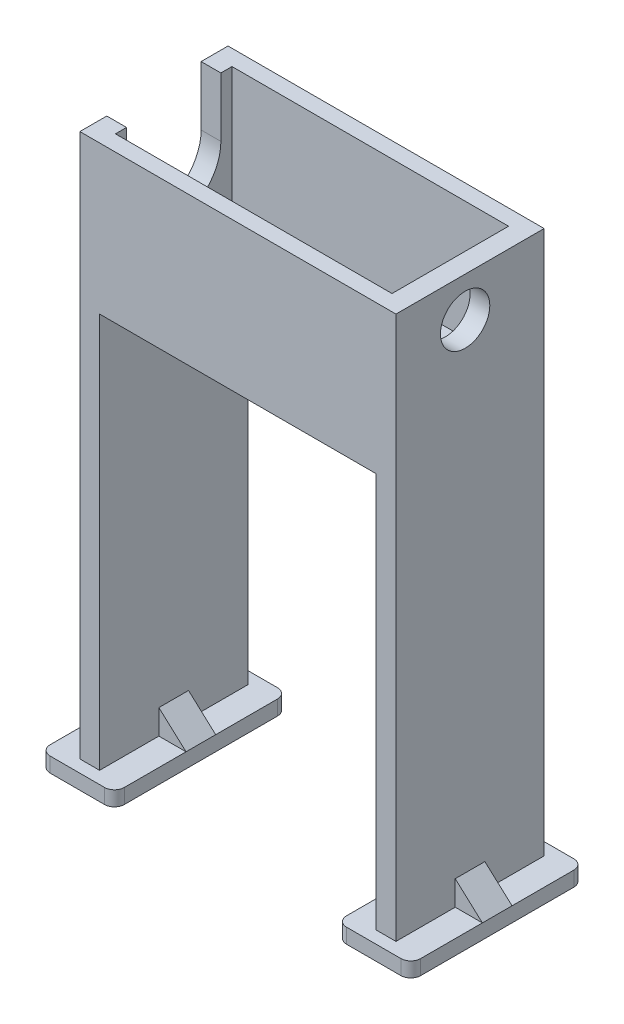
SolidWorks part; units mm, degrees
material "ABS"
ref_plane "Alzado" through (0, 0, 0) normal (0, 0, 1) x (1, 0, 0)
ref_plane "Planta" through (0, 0, 0) normal (0, 1, 0) x (1, 0, 0)
ref_plane "Vista lateral" through (0, 0, 0) normal (1, 0, 0) x (0, 0, -1)
sketch "Croquis2" plane through (0, 0, 0) normal (0, 1, 0) x (1, 0, 0)
  line L0 (30, 22.5259) -> (30, -22.5259) construction
  line L1 (-5.5, -17.5) -> (5.5, -17.5)
  line L2 (-7.5, -15.5) -> (-7.5, 15.5)
  line L3 (-5.5, 17.5) -> (5.5, 17.5)
  line L4 (7.5, -15.5) -> (7.5, 15.5)
  line L5 (-7.5, -17.5) -> (7.5, 17.5) construction
  line L6 (-7.5, 17.5) -> (7.5, -17.5) construction
  line L7 (67.5, 17.5) -> (52.5, -17.5) construction
  line L8 (67.5, -17.5) -> (52.5, 17.5) construction
  line L9 (52.5, -15.5) -> (52.5, 15.5)
  line L10 (65.5, 17.5) -> (54.5, 17.5)
  line L11 (67.5, -15.5) -> (67.5, 15.5)
  line L12 (65.5, -17.5) -> (54.5, -17.5)
  arc A0 (-5.5, -17.5) -> (-7.5, -15.5) centre (-5.5, -15.5) cw
  arc A1 (5.5, -17.5) -> (7.5, -15.5) centre (5.5, -15.5) ccw
  arc A2 (5.5, 17.5) -> (7.5, 15.5) centre (5.5, 15.5) cw
  arc A3 (-7.5, 15.5) -> (-5.5, 17.5) centre (-5.5, 15.5) cw
  arc A4 (67.5, 15.5) -> (65.5, 17.5) centre (65.5, 15.5) ccw
  arc A5 (54.5, 17.5) -> (52.5, 15.5) centre (54.5, 15.5) ccw
  arc A6 (54.5, -17.5) -> (52.5, -15.5) centre (54.5, -15.5) cw
  arc A7 (65.5, -17.5) -> (67.5, -15.5) centre (65.5, -15.5) ccw
  point P0 (0, 0)
  point P36 (60, 0)
  dimension "D4" = 2
  dimension "D1" = 60
  dimension "D2" = 15
  dimension "D3" = 35
extrude "Saliente-Extruir1" add sketch "Croquis2" along normal blind 3
sketch "Croquis3" plane through (0, 0, 0) normal (0, 0, 1) x (1, 0, 0)
  line L0 (-7.5, 3) -> (-2, 8)
  line L1 (-2, 8) -> (-2, 3)
  line L2 (-5.5, 3) -> (5.5, 3) construction
  line L3 (-2, 3) -> (-7.5, 3)
  line L4 (0, 0) -> (0, 24.6277) construction
  line L5 (0, 0) -> (60, 0) construction
  line L6 (54.5, 0) -> (65.5, 0) construction
  line L7 (30, 0) -> (30, 25.119) construction
  line L8 (2, 3) -> (7.5, 3)
  line L9 (2, 8) -> (2, 3)
  line L10 (7.5, 3) -> (2, 8)
  line L11 (52.5, 3) -> (58, 8)
  line L12 (58, 8) -> (58, 3)
  line L13 (58, 3) -> (52.5, 3)
  line L14 (62, 3) -> (67.5, 3)
  line L15 (62, 8) -> (62, 3)
  line L16 (67.5, 3) -> (62, 8)
  dimension "D1" = 5.5
  dimension "D2" = 5
extrude "Saliente-Extruir2" add sketch "Croquis3" along normal blind 3 and the other way blind 3
sketch "Croquis4" plane through (0, 3, 0) normal (0, 1, 0) x (1, 0, 0)
  line L0 (0, 0) -> (60, 0) construction
  line L1 (-2, -15) -> (2, -15)
  line L2 (-2, -15) -> (-2, 15)
  line L3 (-2, 15) -> (2, 15)
  line L4 (2, -15) -> (2, 15)
  line L5 (-2, -15) -> (2, 15) construction
  line L6 (-2, 15) -> (2, -15) construction
  line L7 (30, 0) -> (30, 11.8866) construction
  line L8 (62, 15) -> (58, -15) construction
  line L9 (62, -15) -> (58, 15) construction
  line L10 (58, -15) -> (58, 15)
  line L11 (62, 15) -> (58, 15)
  line L12 (62, -15) -> (62, 15)
  line L13 (62, -15) -> (58, -15)
  line L14 (2, 3) -> (2, -3) construction
  point P0 (0, 0)
  point P14 (60, 0)
  dimension "D1" = 30
  dimension "D2" = 60
  dimension "D3" = 0
extrude "Saliente-Extruir3" add sketch "Croquis4" along normal blind 110
sketch "Croquis5" plane through (2, 0, 0) normal (1, 0, 0) x (0, 0, -1)
  line L0 (0, 113) -> (0, 67.6853) construction
  line L1 (-15, 113) -> (-11.8, 113)
  line L2 (-15, 113) -> (-15, 83)
  line L3 (-15, 83) -> (-11.5, 83)
  line L4 (-11.8, 113) -> (-11.8, 89)
  line L5 (-15, 113) -> (15, 113) construction
  line L6 (11.8, 113) -> (11.8, 89)
  line L7 (15, 83) -> (11.5, 83)
  line L8 (15, 113) -> (15, 83)
  line L9 (15, 113) -> (11.8, 113)
  line L11 (-11.5, 83) -> (11.5, 83)
  line L13 (-11.8, 89) -> (11.8, 89)
  dimension "D1" = 30
  dimension "D2" = 3.5
  dimension "D3" = 6
  dimension "D4" = 3.2
extrude "Saliente-Extruir4" add sketch "Croquis5" along normal up to surface (56 mm away) up to face at (58, 31.75, 0)
sketch "Croquis6" plane through (-2, 0, 0) normal (-1, 0, 0) x (0, 0, 1)
  line L0 (0, 113) -> (0, 89) construction
  line L1 (-15, 113) -> (15, 113) construction
  line L2 (-11.8, 89) -> (11.8, 89) construction
  line L3 (-9.55, 101) -> (-9.55, 113)
  line L4 (-9.55, 113) -> (9.55, 113)
  line L5 (-11.8, 113) -> (11.8, 113) construction
  line L6 (9.55, 113) -> (9.55, 101)
  arc A0 (-9.55, 101) -> (9.55, 101) centre (0, 101) ccw
  dimension "D1" = 19.1
extrude "Cortar-Extruir1" cut sketch "Croquis6" against normal up to surface (4 mm away) up to face at (2, 101, 0)
sketch "Croquis7" plane through (62, 0, 0) normal (1, 0, 0) x (0, 0, -1)
  line L0 (-15, 113) -> (15, 113) construction
  line L3 (-15, 113) -> (-15, 3) construction
  circle A0 centre (-1, 105) radius 5
  dimension "D1" = 10
  dimension "D2" = 8
  dimension "D3" = 14
extrude "Cortar-Extruir2" cut sketch "Croquis7" against normal up to surface (4 mm away) up to face at (58, 101, 0)
